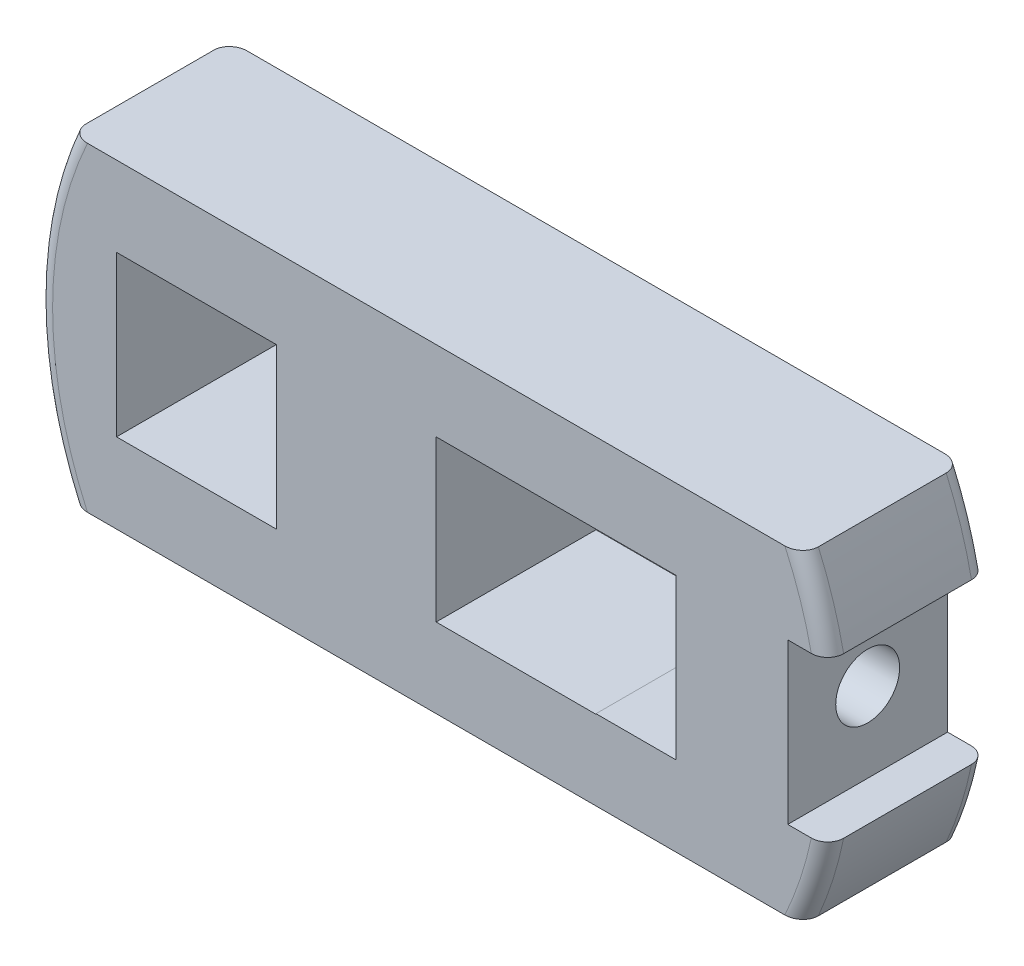
SolidWorks part; units mm, degrees
ref_plane "Front Plane" through (0, 0, 0) normal (0, 0, 1) x (1, 0, 0)
ref_plane "Top Plane" through (0, 0, 0) normal (0, 1, 0) x (1, 0, 0)
ref_plane "Right Plane" through (0, 0, 0) normal (1, 0, 0) x (0, 0, -1)
sketch "Sketch1" plane through (0, 0, 0) normal (0, 0, 1) x (1, 0, 0)
  circle A0 centre (0, 0) radius 25
  dimension "D1" = 50
extrude "Boss-Extrude1" add sketch "Sketch1" along normal blind 10
sketch "Sketch2" plane through (0, 0, 10) normal (0, 0, 1) x (1, 0, 0)
  line L0 (5, -5) -> (15, -5)
  line L1 (-5, -15) -> (5, -15)
  line L2 (-5, -15) -> (-5, -5)
  line L3 (-5, 15) -> (5, 15)
  line L4 (5, -15) -> (5, -5)
  line L5 (-5, -15) -> (5, 15) construction
  line L6 (-5, 15) -> (5, -15) construction
  line L7 (-15, 5) -> (-5, 5)
  line L8 (-15, 5) -> (-15, -5)
  line L9 (-15, -5) -> (-5, -5)
  line L10 (15, 5) -> (15, -5)
  line L11 (-15, 5) -> (15, -5) construction
  line L12 (-15, -5) -> (15, 5) construction
  line L13 (-5, 5) -> (-5, 15)
  line L14 (5, 5) -> (15, 5)
  line L15 (5, 5) -> (5, 15)
  point P0 (0, 0)
  point P5 (0, 0)
  dimension "D1" = 10
  dimension "D2" = 10
  dimension "D3" = 10
  dimension "D4" = 10
extrude "Cut-Extrude1" cut sketch "Sketch2" against normal through all both and the other way through all
sketch "Sketch4" plane through (15, 0, 0) normal (-1, 0, 0) x (0, 0, 1)
  line L0 (0, 5) -> (10, -5) construction
  line L1 (10, -5) -> (10, 5) construction
  line L2 (10, 5) -> (0, -5) construction
  line L4 (4.7591, -4.2656) -> (8.5737, -2.3414)
  line L5 (8.5737, -2.3414) -> (8.8146, 1.9242)
  line L6 (8.8146, 1.9242) -> (5.2409, 4.2656)
  line L7 (5.2409, 4.2656) -> (1.4263, 2.3414)
  line L8 (1.4263, 2.3414) -> (1.1854, -1.9242)
  line L9 (1.1854, -1.9242) -> (4.7591, -4.2656)
  circle A0 centre (5, 0) radius 3.7 construction
extrude "Cut-Extrude2" cut sketch "Sketch4" against normal blind 3
sketch "Sketch5" plane through (18, 0, 0) normal (-1, 0, 0) x (0, 0, 1)
  line L0 (5.2409, 4.2656) -> (4.7591, -4.2656) construction
  circle A0 centre (5, 0) radius 2
  dimension "D1" = 4
extrude "Cut-Extrude4" cut sketch "Sketch5" against normal blind 13 contours A0
fillet "Fillet1" radius 1 2 edges at (25, 0, 0) (25, 0, 10)
sketch3d "3DSketch1"
  spline S0 degree 3 poles (25, -0.2644, 7) (25, 0.1322, 7) (24.999, 0.2622, 6.987) (24.995, 0.5178, 6.9362) (24.992, 0.6449, 6.8977) (24.9846, 0.8871, 6.7973) (24.9802, 1.0019, 6.7359) (24.9705, 1.2193, 6.5907) (24.9652, 1.3221, 6.5063) (24.9495, 1.5988, 6.2296) (24.939, 1.7478, 6.0066) (24.9242, 1.9473, 5.5253) (24.9199, 1.9999, 5.2621) (24.9199, 2.0001, 4.8706) (24.9209, 1.9871, 4.738) (24.9249, 1.936, 4.4815) (24.9279, 1.8983, 4.3568) (24.9353, 1.7981, 4.1146) (24.9398, 1.7355, 3.9975) (24.9494, 1.5908, 3.7809) (24.9546, 1.5082, 3.6798) (24.9652, 1.3216, 3.493) (24.9704, 1.2205, 3.4102) (24.9801, 1.004, 3.2654) (24.9845, 0.8871, 3.2027) (24.992, 0.6449, 3.1023) (24.9949, 0.5202, 3.0644) (24.9989, 0.2639, 3.0132) (25, 0.1313, 3) (25, -0.2604, 2.9999) (24.9957, -0.5236, 3.0522) (24.9809, -1.0051, 3.2514) (24.9705, -1.2283, 3.4002) (24.9548, -1.5051, 3.6765) (24.9495, -1.5896, 3.7793) (24.9398, -1.735, 3.9966) (24.9354, -1.7965, 4.1114) (24.928, -1.8971, 4.3533) (24.925, -1.9357, 4.4804) (24.9209, -1.9868, 4.7361) (24.9199, -1.9999, 4.866) (24.9199, -2.0001, 5.1301) (24.9209, -1.9873, 5.2604) (24.9249, -1.9367, 5.5161) (24.9279, -1.8983, 5.643) (24.9353, -1.7981, 5.8855) (24.9397, -1.7367, 6.0004) (24.9494, -1.5919, 6.2178) (24.9547, -1.5075, 6.3208) (24.9704, -1.231, 6.5977) (24.9808, -1.0081, 6.7469) (24.9956, -0.527, 6.9468) (25, -0.2644, 7) (25, 0.1322, 7) (24.999, 0.2622, 6.987) knots -0.0625 -0.0625 0 0 0.03125 0.03125 0.0625 0.0625 0.09375 0.09375 0.125 0.125 0.1875 0.1875 0.25 0.25 0.28125 0.28125 0.3125 0.3125 0.34375 0.34375 0.375 0.375 0.40625 0.40625 0.4375 0.4375 0.46875 0.46875 0.5 0.5 0.5625 0.5625 0.625 0.625 0.65625 0.65625 0.6875 0.6875 0.71875 0.71875 0.75 0.75 0.78125 0.78125 0.8125 0.8125 0.84375 0.84375 0.875 0.875 0.9375 0.9375 1 1 1.03125 1.03125 1.0625 only from (25, 0, 7) to (25, 0, 7) construction
  point P0 (24.927, 1.9093, 5.5951)
sketch3d "3DSketch2"
  spline S0 degree 3 poles (25, -0.2644, 7) (25, 0.1322, 7) (24.999, 0.2622, 6.987) (24.995, 0.5178, 6.9362) (24.992, 0.6449, 6.8977) (24.9846, 0.8871, 6.7973) (24.9802, 1.0019, 6.7359) (24.9705, 1.2193, 6.5907) (24.9652, 1.3221, 6.5063) (24.9495, 1.5988, 6.2296) (24.939, 1.7478, 6.0066) (24.9242, 1.9473, 5.5253) (24.9199, 1.9999, 5.2621) (24.9199, 2.0001, 4.8706) (24.9209, 1.9871, 4.738) (24.9249, 1.936, 4.4815) (24.9279, 1.8983, 4.3568) (24.9353, 1.7981, 4.1146) (24.9398, 1.7355, 3.9975) (24.9494, 1.5908, 3.7809) (24.9546, 1.5082, 3.6798) (24.9652, 1.3216, 3.493) (24.9704, 1.2205, 3.4102) (24.9801, 1.004, 3.2654) (24.9845, 0.8871, 3.2027) (24.992, 0.6449, 3.1023) (24.9949, 0.5202, 3.0644) (24.9989, 0.2639, 3.0132) (25, 0.1313, 3) (25, -0.2604, 2.9999) (24.9957, -0.5236, 3.0522) (24.9809, -1.0051, 3.2514) (24.9705, -1.2283, 3.4002) (24.9548, -1.5051, 3.6765) (24.9495, -1.5896, 3.7793) (24.9398, -1.735, 3.9966) (24.9354, -1.7965, 4.1114) (24.928, -1.8971, 4.3533) (24.925, -1.9357, 4.4804) (24.9209, -1.9868, 4.7361) (24.9199, -1.9999, 4.866) (24.9199, -2.0001, 5.1301) (24.9209, -1.9873, 5.2604) (24.9249, -1.9367, 5.5161) (24.9279, -1.8983, 5.643) (24.9353, -1.7981, 5.8855) (24.9397, -1.7367, 6.0004) (24.9494, -1.5919, 6.2178) (24.9547, -1.5075, 6.3208) (24.9704, -1.231, 6.5977) (24.9808, -1.0081, 6.7469) (24.9956, -0.527, 6.9468) (25, -0.2644, 7) (25, 0.1322, 7) (24.999, 0.2622, 6.987) knots -0.0625 -0.0625 0 0 0.03125 0.03125 0.0625 0.0625 0.09375 0.09375 0.125 0.125 0.1875 0.1875 0.25 0.25 0.28125 0.28125 0.3125 0.3125 0.34375 0.34375 0.375 0.375 0.40625 0.40625 0.4375 0.4375 0.46875 0.46875 0.5 0.5 0.5625 0.5625 0.625 0.625 0.65625 0.65625 0.6875 0.6875 0.71875 0.71875 0.75 0.75 0.78125 0.78125 0.8125 0.8125 0.84375 0.84375 0.875 0.875 0.9375 0.9375 1 1 1.03125 1.03125 1.0625 only from (25, 0, 7) to (25, 0, 7) construction
  point P0 (24.9992, 0.2052, 3.0106)
ref_plane "Plane2" through (24.9992, 0, 0) normal (1, 0, 0) x (0, 1, 0)
sketch "Sketch6" plane through (24.9992, 0, 0) normal (1, 0, 0) x (0, 1, 0)
  line L0 (0, 5) -> (0, -3.3415) construction
  line L2 (-5, 10) -> (5, 10)
  line L3 (-5, 10) -> (-5, 0)
  line L4 (-5, 0) -> (5, 0)
  line L5 (5, 10) -> (5, 0)
  line L6 (-5, 10) -> (5, 0) construction
  line L7 (-5, 0) -> (5, 10) construction
  dimension "D1" = 10
  dimension "D2" = 10
extrude "Cut-Extrude6" cut sketch "Sketch6" against normal blind 3 and the other way blind 3
sketch "Sketch7" plane through (0, 0, 0) normal (0, 0, -1) x (-1, 0, 0)
  line L1 (-5, 15) -> (5, 15)
  line L2 (-5, 15) -> (-5, -15)
  line L3 (-5, -15) -> (5, -15)
  line L4 (5, 15) -> (5, -15)
extrude "Boss-Extrude2" add sketch "Sketch7" against normal blind 10
sketch "Sketch8" plane through (0, 0, 0) normal (0, 0, -1) x (-1, 0, 0)
  line L1 (5, 5) -> (15, 5)
  line L2 (5, 5) -> (5, -5)
  line L3 (5, -5) -> (15, -5)
  line L4 (15, 5) -> (15, -5)
extrude "Boss-Extrude3" add sketch "Sketch8" against normal blind 10
sketch "Sketch9" plane through (0, 0, 0) normal (0, 0, -1) x (-1, 0, 0)
  line L0 (0, 0) -> (0, 15) construction
  line L1 (0, 0) -> (15, 0) construction
  line L3 (20, 5) -> (10, 5)
  line L4 (20, 5) -> (20, -5)
  line L5 (20, -5) -> (10, -5)
  line L6 (10, 5) -> (10, -5)
  line L7 (20, 5) -> (10, -5) construction
  line L8 (20, -5) -> (10, 5) construction
  dimension "D1" = 15
  dimension "D2" = 15
  dimension "D3" = 10
extrude "Cut-Extrude7" cut sketch "Sketch9" against normal blind 10 contours L4 L3 L6 L5
sketch "Sketch10" plane through (0, 0, 0) normal (0, 0, -1) x (-1, 0, 0)
  line L0 (0, 0) -> (0, 10) construction
  line L1 (0, 10) -> (0, -10) construction
  line L3 (-40.8768, 38.8544) -> (42.8671, 38.8544)
  line L4 (-40.8768, 38.8544) -> (-40.8768, 10)
  line L5 (-40.8768, 10) -> (42.8671, 10)
  line L6 (42.8671, 38.8544) -> (42.8671, 10)
  line L7 (-44.7783, -36.2349) -> (37.6828, -36.2349)
  line L8 (-44.7783, -36.2349) -> (-44.7783, -10)
  line L9 (-44.7783, -10) -> (37.6828, -10)
  line L10 (37.6828, -36.2349) -> (37.6828, -10)
  dimension "D1" = 20
  dimension "D2" = 10
extrude "Cut-Extrude8" cut sketch "Sketch10" against normal blind 10
sketch "Sketch11" plane through (0, 0, 0) normal (0, 0, -1) x (-1, 0, 0)
  line L0 (-15, 5) -> (-5, 5) construction
  line L1 (-10, 5) -> (0, 5)
  line L2 (-10, 5) -> (-10, -5.0327)
  line L3 (-10, -5.0327) -> (0, -5.0327)
  line L4 (0, 5) -> (0, -5.0327)
  dimension "D1" = 10
  dimension "D2" = 10.0327
extrude "Cut-Extrude9" cut sketch "Sketch11" against normal blind 10
